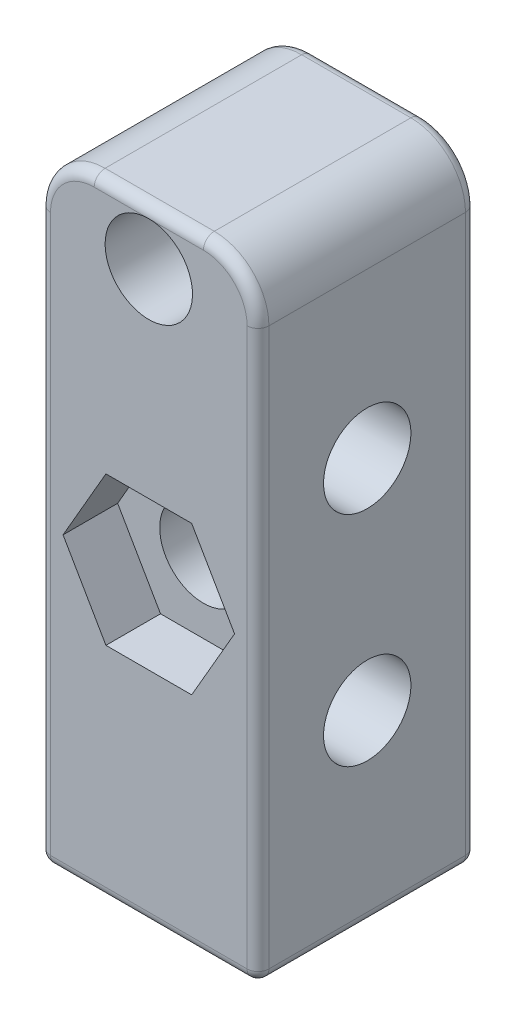
SolidWorks part; units mm, degrees
ref_plane "Alzado" through (0, 0, 0) normal (0, 0, 1) x (1, 0, 0)
ref_plane "Planta" through (0, 0, 0) normal (0, 1, 0) x (1, 0, 0)
ref_plane "Vista lateral" through (0, 0, 0) normal (1, 0, 0) x (0, 0, -1)
sketch "Croquis1" plane through (0, 0, 0) normal (0, 1, 0) x (1, 0, 0)
  line L1 (0, 0) -> (20, 0)
  line L2 (0, 0) -> (0, 20)
  line L3 (0, 20) -> (20, 20)
  line L4 (20, 0) -> (20, 20)
  dimension "D1" = 20
  dimension "D2" = 20
extrude "Saliente-Extruir1" add sketch "Croquis1" along normal blind 50 and the other way blind 7
sketch "Croquis2" plane through (0, 0, 0) normal (0, 0, 1) x (1, 0, 0)
  line L0 (0, 50) -> (0, -7) construction
  line L1 (0, 50) -> (20, 50) construction
  circle A0 centre (10, 45) radius 4
  circle A1 centre (10, 20) radius 4
  dimension "D1" = 8
  dimension "D2" = 8
  dimension "D3" = 10
  dimension "D4" = 5
  dimension "D5" = 25
extrude "Cortar-Extruir1" cut sketch "Croquis2" against normal through all
sketch "Croquis3" plane through (0, 0, 0) normal (0, 0, 1) x (1, 0, 0)
  line L1 (13.926, 26.8) -> (6.074, 26.8)
  line L2 (6.074, 26.8) -> (2.148, 20)
  line L3 (2.148, 20) -> (6.074, 13.2)
  line L4 (6.074, 13.2) -> (13.926, 13.2)
  line L5 (13.926, 13.2) -> (17.852, 20)
  line L6 (17.852, 20) -> (13.926, 26.8)
  circle A0 centre (10, 20) radius 7.852 construction
  dimension "D1" = 13.6
extrude "Cortar-Extruir2" cut sketch "Croquis3" against normal blind 5
sketch "Croquis4" plane through (0, 0, 0) normal (-1, 0, 0) x (0, 0, 1)
  line L0 (-20, 45) -> (0, 45) construction
  line L1 (-20, 50) -> (-20, -7) construction
  circle A0 centre (-10, 30) radius 4
  circle A1 centre (-10, 10) radius 4
  dimension "D1" = 8
  dimension "D2" = 8
  dimension "D5" = 10
  dimension "D3" = 15
  dimension "D4" = 20
extrude "Cortar-Extruir3" cut sketch "Croquis4" against normal through all
sketch "Croquis5" plane through (0, 0, 0) normal (-1, 0, 0) x (0, 0, 1)
  line L1 (-6.074, 23.2) -> (-2.148, 30)
  line L2 (-2.148, 30) -> (-6.074, 36.8)
  line L3 (-6.074, 36.8) -> (-13.926, 36.8)
  line L4 (-13.926, 36.8) -> (-17.852, 30)
  line L5 (-17.852, 30) -> (-13.926, 23.2)
  line L6 (-13.926, 23.2) -> (-6.074, 23.2)
  line L7 (-6.074, 16.8) -> (-13.926, 16.8)
  line L8 (-13.926, 16.8) -> (-17.852, 10)
  line L9 (-17.852, 10) -> (-13.926, 3.2)
  line L10 (-13.926, 3.2) -> (-6.074, 3.2)
  line L11 (-6.074, 3.2) -> (-2.148, 10)
  line L12 (-2.148, 10) -> (-6.074, 16.8)
  circle A0 centre (-10, 30) radius 6.8 construction
  circle A1 centre (-10, 10) radius 6.8 construction
  dimension "D1" = 13.6
  dimension "D2" = 13.6
extrude "Cortar-Extruir4" cut sketch "Croquis5" against normal blind 5
fillet "Redondeo1" radius 5 2 edges at (20, 50, -10) (0, 50, -10)
fillet "Redondeo2" radius 1 4 edges at (0, -7, -10) (10, -7, -20) (20, -7, -10) (10, -7, 0)
fillet "Redondeo3" radius 1 14 edges at (0.2929, -6.7071, -19.7071) (0, 19.5, -20) (1.4645, 48.5355, -20) (10, 50, -20) (18.5355, 48.5355, -20) (19.7071, -6.7071, -19.7071) (19.7071, -6.7071, -0.2929) (20, 19.5, 0) (18.5355, 48.5355, 0) (10, 50, 0) (1.4645, 48.5355, 0) (0.2929, -6.7071, -0.2929) (20, 19.5, -20) (0, 19.5, 0)
